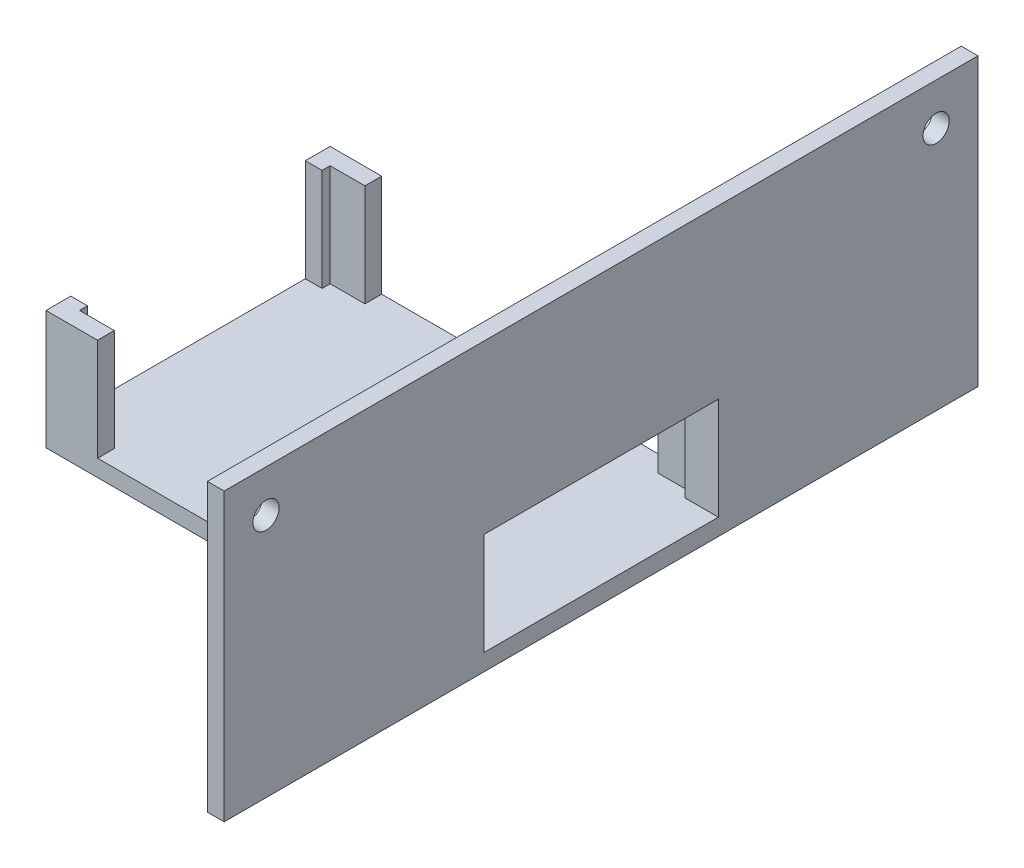
SolidWorks part; units mm, degrees
material "ABS"
ref_plane "Front Plane" through (0, 0, 0) normal (0, 0, 1) x (1, 0, 0)
ref_plane "Top Plane" through (0, 0, 0) normal (0, 1, 0) x (1, 0, 0)
ref_plane "Right Plane" through (0, 0, 0) normal (1, 0, 0) x (0, 0, -1)
sketch "Sketch1" plane through (0, 0, 0) normal (0, 1, 0) x (1, 0, 0)
  line L1 (-30.04, 43.08) -> (30.04, 43.08)
  line L2 (-30.04, 43.08) -> (-30.04, 0)
  line L3 (-30.04, 0) -> (30.04, 0)
  line L4 (30.04, 43.08) -> (30.04, 0)
  dimension "D1" = 60.08
  dimension "D2" = 43.08
extrude "Boss-Extrude1" add sketch "Sketch1" along normal blind 18.04
shell "Shell1" thickness 2.54 removed face at (0, 18.04, -21.54)
sketch "Sketch2" plane through (30.04, 0, 0) normal (1, 0, 0) x (0, 0, -1)
  line L0 (0, 0) -> (43.08, 0) construction
  line L1 (78.69, 0) -> (-35.61, 0)
  line L2 (78.69, 0) -> (78.69, 43.44)
  line L3 (78.69, 43.44) -> (-35.61, 43.44)
  line L4 (-35.61, 0) -> (-35.61, 43.44)
  line L6 (0, 18.04) -> (43.08, 18.04) construction
  point P7 (21.54, 0)
  point P8 (21.54, 0)
  dimension "D1" = 25.4
  dimension "D2" = 114.3
extrude "Boss-Extrude2" add sketch "Sketch2" along normal blind 2.54
fillet "Fillet1" radius 5.08 1 edges at (30.04, 18.04, -21.54)
sketch "Sketch3" plane through (30.04, 0, 0) normal (-1, 0, 0) x (0, 0, 1)
  line L0 (-78.69, 0) -> (-78.69, 43.44) construction
  line L1 (-78.69, 43.44) -> (35.61, 43.44) construction
  line L2 (35.61, 43.44) -> (35.61, 0) construction
  circle A0 centre (-72.34, 37.09) radius 1.9844
  circle A1 centre (29.26, 37.09) radius 1.9844
  dimension "D1" = 3.9688
  dimension "D2" = 6.35
  dimension "D3" = 6.35
  dimension "D4" = 6.35
  dimension "D5" = 6.35
extrude "Cut-Extrude1" cut sketch "Sketch3" against normal through all both and the other way through all
sketch "Sketch5" plane through (0, 0, 0) normal (0, 0, 1) x (1, 0, 0)
  line L0 (0, -23.892) -> (0, 23.892) construction
  line L1 (22.225, 2.54) -> (-22.225, 2.54)
  line L2 (22.225, 2.54) -> (22.225, 18.04)
  line L3 (22.225, 18.04) -> (-22.225, 18.04)
  line L4 (-22.225, 2.54) -> (-22.225, 18.04)
  line L5 (22.225, 2.54) -> (-22.225, 18.04) construction
  line L6 (22.225, 18.04) -> (-22.225, 2.54) construction
  line L11 (-30.04, 18.04) -> (24.96, 18.04) construction
  line L12 (-27.5, 2.54) -> (27.5, 2.54) construction
  point P0 (0, 10.29)
  dimension "D1" = 44.45
extrude "Cut-Extrude2" cut sketch "Sketch5" against normal through all
sketch "Sketch6" plane through (-30.04, 0, 0) normal (-1, 0, 0) x (0, 0, 1)
  line L0 (-43.08, 18.04) -> (0, 18.04) construction
  line L1 (-3.76, 2.54) -> (-39.32, 2.54)
  line L2 (-3.76, 2.54) -> (-3.76, 18.04)
  line L3 (-3.76, 18.04) -> (-39.32, 18.04)
  line L4 (-39.32, 2.54) -> (-39.32, 18.04)
  line L5 (-3.76, 2.54) -> (-39.32, 18.04) construction
  line L6 (-3.76, 18.04) -> (-39.32, 2.54) construction
  line L7 (-40.54, 2.54) -> (-2.54, 2.54) construction
  line L8 (-21.54, 0) -> (-21.54, 18.04) construction
  line L9 (-43.08, 0) -> (0, 0) construction
  point P0 (-21.54, 10.29)
  dimension "D1" = 35.56
extrude "Cut-Extrude3" cut sketch "Sketch6" against normal through all
fillet "Fillet2" radius 5.08 2 edges at (30.04, 11.56, -43.08) (30.04, 11.56, 0)
